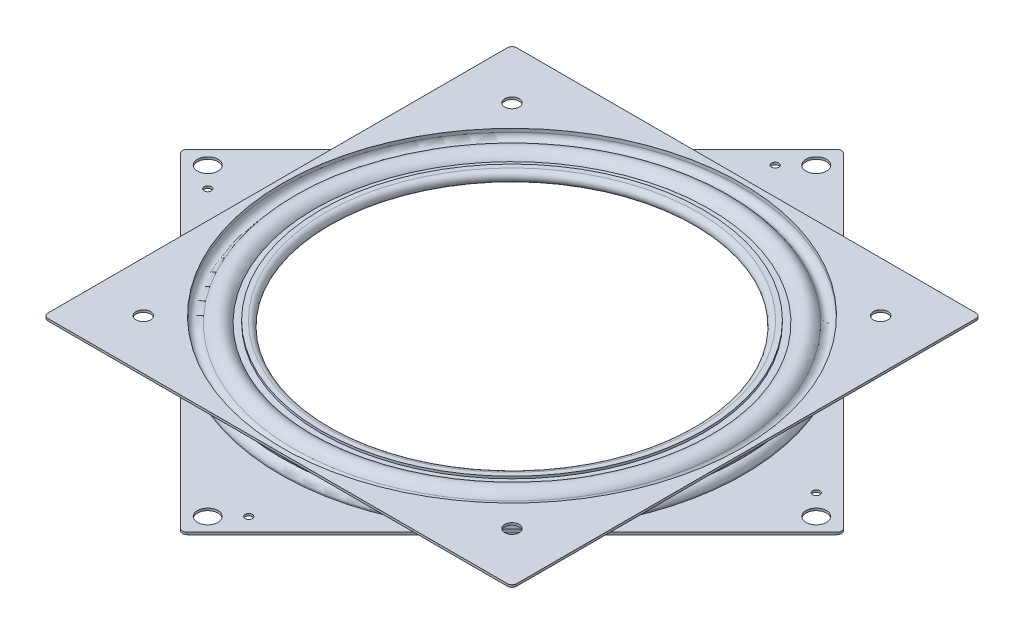
SolidWorks part; units mm, degrees
note: The reader was unsure of these and kept them because the rebuilt part matched: shared geometry of "Sketch3<3>".
ref_plane "Front Plane" through (0, 0, 0) normal (0, 0, 1) x (1, 0, 0)
ref_plane "Top Plane" through (0, 0, 0) normal (0, 1, 0) x (1, 0, 0)
ref_plane "Right Plane" through (0, 0, 0) normal (1, 0, 0) x (0, 0, -1)
sketch "Sketch1" plane through (0, 0, 0) normal (0, 1, 0) x (1, 0, 0)
  line L0 (0, -108.8407) -> (-108.8407, 0) construction
  line L1 (-76.962, 76.962) -> (76.962, 76.962) construction
  line L2 (-76.962, 76.962) -> (-76.962, -76.962) construction
  line L3 (-76.962, -76.962) -> (76.962, -76.962) construction
  line L4 (76.962, 76.962) -> (76.962, -76.962) construction
  line L5 (0, -76.962) -> (0, 76.962) construction
  line L6 (-76.962, 0) -> (76.962, 0) construction
  line L7 (0, -108.8407) -> (108.8407, 0) construction
  line L8 (-108.8407, 0) -> (0, 108.8407) construction
  line L9 (108.8407, 0) -> (0, 108.8407) construction
  line L10 (0, -108.8407) -> (0, 108.8407) construction
  line L11 (-108.8407, 0) -> (108.8407, 0) construction
  line L12 (76.962, -76.962) -> (-76.962, 76.962) construction
  line L13 (76.962, 76.962) -> (-76.962, -76.962) construction
  line L14 (-99.9053, 0) -> (0, 99.9053) construction
  line L19 (-60.5282, 60.5282) -> (60.5282, 60.5282) construction
  line L20 (-60.5282, 60.5282) -> (-60.5282, -60.5282) construction
  line L21 (-60.5282, -60.5282) -> (60.5282, -60.5282) construction
  line L22 (60.5282, 60.5282) -> (60.5282, -60.5282) construction
  line L23 (-99.9053, 0) -> (0, -99.9053) construction
  line L24 (0, 99.9053) -> (99.9053, 0) construction
  line L25 (0, -99.9053) -> (99.9053, 0) construction
  line L26 (-6.7352, 93.1702) -> (0, 99.9053) construction
  line L27 (-99.9053, 0) -> (-93.1702, -6.7352) construction
  line L28 (0, -99.9053) -> (6.7352, -93.1702) construction
  line L29 (93.1702, 6.7352) -> (99.9053, 0) construction
  circle A0 centre (0, 0) radius 59.436 construction
  circle A1 centre (60.5282, -60.5282) radius 2.3813 construction
  circle A2 centre (-60.5282, -60.5282) radius 2.3812 construction
  circle A3 centre (-60.5282, 60.5282) radius 2.3812 construction
  circle A4 centre (60.5282, 60.5282) radius 2.3813 construction
  circle A9 centre (-99.9053, 0) radius 3.3734 construction
  circle A10 centre (0, 99.9053) radius 3.3734 construction
  circle A11 centre (99.9053, 0) radius 3.3734 construction
  circle A12 centre (0, -99.9053) radius 3.3734 construction
  circle A13 centre (-93.1702, -6.7352) radius 1.1922 construction
  circle A14 centre (6.7352, -93.1702) radius 1.1922 construction
  circle A15 centre (93.1702, 6.7352) radius 1.1922 construction
  circle A16 centre (-6.7352, 93.1702) radius 1.1922 construction
  dimension "ID" = 118.872
  dimension "Top Mounting Hole Dia." = 4.7625
  dimension "Bottom Outer Mounting Hole Dia." = 6.7469
  dimension "Bottom Inner Mounting Hole Dia." = 2.3844
  dimension "Length" = 153.924
  dimension "Width" = 153.924
  dimension "Top Mounting Length" = 121.0564
  dimension "Bottom Outer Mounting Length" = 141.2875
  dimension "Bottom Hole Spacing" = 9.525
sketch "Sketch2" plane through (0, 0, 0) normal (0, 0, 1) x (1, 0, 0)
  line L0 (0, 3.937) -> (0, -3.937) construction
  line L1 (-76.962, 3.937) -> (76.962, 3.937) construction
  line L2 (-76.962, 3.937) -> (-76.962, -3.937) construction
  line L3 (-76.962, -3.937) -> (76.962, -3.937) construction
  line L4 (76.962, 3.937) -> (76.962, -3.937) construction
  line L5 (-76.962, 0) -> (76.962, 0) construction
  line L6 (-76.962, 3.2004) -> (76.962, 3.2004) construction
  line L7 (-76.962, -3.2004) -> (76.962, -3.2004) construction
  point P8 (0, 0)
  dimension "Overall Height" = 7.874
  dimension "Plate Thickness" = 0.7366
sketch "Sketch3" plane through (0, 0, 0) normal (0, 0, 1) x (1, 0, 0)
  line L0 (76.962, 3.937) -> (75.3482, 3.937)
  line L1 (-76.962, 3.937) -> (76.962, 3.937) construction
  line L2 (75.3482, 3.937) -> (75.3482, 2.8346)
  line L3 (64.7735, 1.9406) -> (61.2076, 1.9406)
  line L4 (76.962, -3.937) -> (75.3482, -3.937)
  line L5 (-76.962, -3.937) -> (76.962, -3.937) construction
  line L6 (75.3482, -3.937) -> (75.3482, -2.8346)
  line L7 (75.3482, -2.8346) -> (75.3482, 2.8346) construction
  line L8 (64.3585, -0.8661) -> (61.2076, -0.8661)
  line L9 (61.2076, 2.6772) -> (62.7831, 2.6772)
  line L10 (64.3585, -0.8661) -> (75.3482, -0.8661) construction
  line L11 (59.436, 3.937) -> (59.436, -3.937) construction
  line L12 (59.436, 0) -> (-59.436, 0) construction
  line L13 (61.2076, 2.6772) -> (61.2076, 1.9406) construction
  line L14 (76.962, -3.937) -> (76.962, 3.937) construction
  line L15 (68.199, 0) -> (76.962, 0) construction
  line L16 (68.199, 0) -> (59.436, 0) construction
  line L17 (76.962, 3.937) -> (76.962, -3.937) construction
  line L18 (62.7831, -0.8661) -> (62.7831, 2.6772) construction
  line L19 (0, 3.937) -> (0, -3.937) construction
  arc A0 (75.3482, 2.8346) -> (71.6528, 1.8898) centre (73.3797, 2.8346) cw
  circle A1 centre (68.199, 0) radius 3.937 construction
  arc A2 (71.6528, 1.8898) -> (64.7735, 1.9406) centre (68.199, 0) ccw
  arc A3 (75.3482, -2.8346) -> (71.6528, -1.8898) centre (73.3797, -2.8346) ccw
  arc A4 (71.6528, -1.8898) -> (64.3585, -0.8661) centre (68.199, 0) cw
  arc A5 (61.2076, -0.8661) -> (61.2076, 2.6772) centre (61.2076, 0.9055) cw
  point P26 (59.436, 0)
  point P38 (61.9954, 2.6772)
  dimension "D3" = 7.874
  dimension "D4" = 1.9685
  dimension "D1" = 0.7366
  dimension "D2" = 3.5433
  dimension "D5" = 6.6142
  dimension "D6" = 1.6138
revolve "Revolve-Thin1" add sketch "Sketch3" angle 360 about L0
revolve "Revolve-Thin2" add sketch "Sketch3<3>" angle 360 about L0
sketch "Sketch3<3>" plane through (0, 0, 0) normal (0, 0, 1) x (1, 0, 0) same geometry as "Sketch3"
sketch "Sketch4" plane through (0, 3.937, 0) normal (0, 1, 0) x (1, 0, 0)
  line L1 (-76.962, 76.962) -> (76.962, 76.962)
  line L2 (-76.962, 76.962) -> (-76.962, -76.962)
  line L3 (-76.962, -76.962) -> (76.962, -76.962)
  line L4 (76.962, 76.962) -> (76.962, -76.962)
  circle A0 centre (0, 0) radius 75.3482 construction
  circle A1 centre (0, 0) radius 75.3482
extrude "Boss-Extrude1" add sketch "Sketch4" against normal up to vertex (0.7366 mm away) up to point (76.962, 3.2004, 0)
sketch "Sketch5" plane through (0, -3.937, 0) normal (0, -1, 0) x (1, 0, 0)
  line L0 (-108.8407, 0) -> (0, 108.8407)
  line L1 (0, 108.8407) -> (108.8407, 0)
  line L2 (108.8407, 0) -> (0, -108.8407)
  line L3 (0, -108.8407) -> (-108.8407, 0)
  circle A0 centre (0, 0) radius 75.3482 construction
  circle A1 centre (0, 0) radius 75.3482
extrude "Boss-Extrude2" add sketch "Sketch5" against normal up to vertex (0.7366 mm away) up to point (-76.962, -3.2004, 0)
sketch "Sketch6" plane through (0, 0, 0) normal (0, 1, 0) x (1, 0, 0)
  circle A0 centre (-60.5282, 60.5282) radius 2.3812 construction
  circle A1 centre (-60.5282, -60.5282) radius 2.3813 construction
  circle A2 centre (60.5282, -60.5282) radius 2.3813 construction
  circle A3 centre (60.5282, 60.5282) radius 2.3813 construction
  circle A4 centre (-60.5282, 60.5282) radius 2.3812
  circle A5 centre (-60.5282, -60.5282) radius 2.3812
  circle A6 centre (60.5282, -60.5282) radius 2.3813
  circle A7 centre (60.5282, 60.5282) radius 2.3813
extrude "Cut-Extrude1" cut sketch "Sketch6" against normal through all both and the other way through all
sketch "Sketch7" plane through (0, 0, 0) normal (0, 1, 0) x (1, 0, 0)
  line L0 (-99.9053, 0) -> (0, 99.9053) construction
  line L1 (-99.9053, 0) -> (0, -99.9053) construction
  line L2 (0, 99.9053) -> (99.9053, 0) construction
  line L3 (0, -99.9053) -> (99.9053, 0) construction
  line L4 (-99.9053, 0) -> (99.9053, 0) construction
  line L5 (0, 99.9053) -> (0, -99.9053) construction
  line L6 (-108.8407, 0) -> (108.8407, 0) construction
  line L7 (0, -108.8407) -> (0, 108.8407) construction
  circle A0 centre (99.9053, 0) radius 3.3734
  circle A1 centre (0, 99.9053) radius 3.3734
  circle A2 centre (-99.9053, 0) radius 3.3734
  circle A3 centre (0, -99.9053) radius 3.3734
  circle A6 centre (0, -99.9053) radius 3.3734 construction
  circle A7 centre (6.7352, -93.1702) radius 1.1922 construction
  circle A8 centre (6.7352, -93.1702) radius 1.1922
  circle A9 centre (-93.1702, -6.7352) radius 1.1922 construction
  circle A10 centre (-6.7352, 93.1702) radius 1.1922 construction
  circle A11 centre (93.1702, 6.7352) radius 1.1922 construction
  circle A12 centre (-93.1702, -6.7352) radius 1.1922
  circle A13 centre (-6.7352, 93.1702) radius 1.1922
  circle A14 centre (93.1702, 6.7352) radius 1.1922
  point P1 (0, 0)
extrude "Cut-Extrude2" cut sketch "Sketch7" against normal through all both and the other way through all
sketch "Sketch8" plane through (0, 0, 0) normal (0, 0, 1) x (1, 0, 0)
  line L0 (68.199, -3.683) -> (68.199, 3.683)
  arc A1 (68.199, 3.683) -> (68.199, -3.683) centre (68.199, 0) cw
  circle A2 centre (68.199, 0) radius 3.683
  circle A3 centre (68.199, 0) radius 3.683 construction
  dimension "D1" = 0.254
revolve "Revolve1" add sketch "Sketch8" angle 360 about L0
pattern_circular "CirPattern1" count 50 over 360 about axis through (0, 0, 0) along (0, 1, 0) of bodies 110
fillet "Fillet1" radius 1.5392 4 edges at (-76.962, 3.5687, -76.962) (76.962, 3.5687, -76.962) (-76.962, 3.5687, 76.962) (76.962, 3.5687, 76.962)
fillet "Fillet2" radius 1.5392 4 edges at (-108.8407, -3.5687, 0) (0, -3.5687, -108.8407) (108.8407, -3.5687, 0) (0, -3.5687, 108.8407)
equation "\"D1@Sketch3\"=\"Plate Thickness@Sketch2\""
equation "\"D2@Sketch3\"=\"Overall Height@Sketch2\"*.45"
equation "\"D5@Sketch3\"=\"Overall Height@Sketch2\"*.84"
equation "\"D4@Sketch3\"=\"D3@Sketch3\"*.25"
equation "\"D3@Revolve-Thin2\"=\"Plate Thickness@Sketch2\""
equation "\"D3@Revolve-Thin1\"=\"Plate Thickness@Sketch2\""
equation "\"D1@Fillet2\"=\"D1@Fillet1\""
equation "\"D1@Fillet1\"=\"Length@Sketch1\"*.01"
